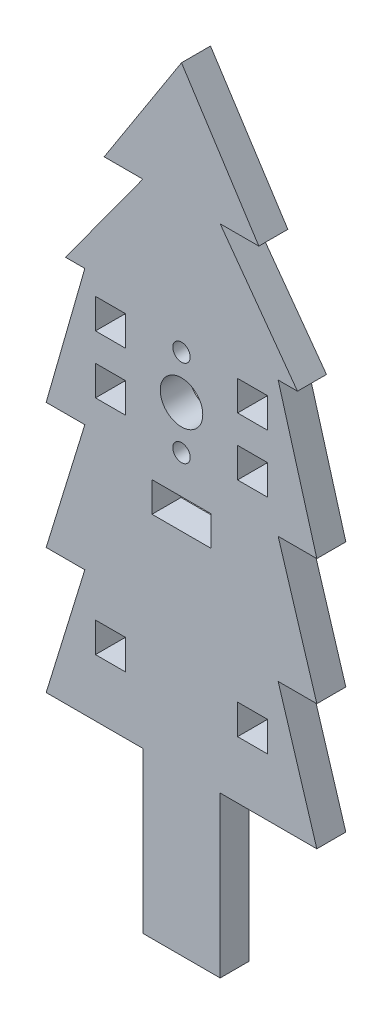
SolidWorks part; units mm, degrees
ref_plane "Ebene vorne (XY)" through (0, 0, 0) normal (0, 0, 1) x (1, 0, 0)
ref_plane "Ebene oben  (XZ)" through (0, 0, 0) normal (0, 1, 0) x (1, 0, 0)
ref_plane "Ebene rechts  (YZ)" through (0, 0, 0) normal (1, 0, 0) x (0, 0, -1)
ref_axis "x-Achse" through (-15.4, 0, 0) along (1, 0, 0)
ref_axis "y-Achse" through (0, 34.4272, 0) along (0, -1, 0)
ref_axis "z-Achse" through (0, 0, -0.15) along (0, 0, 1)
sketch "Profile_Laser_profile_3mm" plane through (0, 0, 0) normal (0, 0, 1) x (1, 0, 0)
  line L0 (0, 30.4272) -> (8, 18)
  line L1 (8, 18) -> (4, 18)
  line L2 (4, 18) -> (12, 7)
  line L3 (12, 7) -> (10, 7)
  line L4 (10, 7) -> (14, -7)
  line L5 (14, -7) -> (10, -7)
  line L6 (10, -7) -> (14, -20)
  line L7 (14, -20) -> (10, -20)
  line L8 (10, -20) -> (14, -33)
  line L9 (14, -33) -> (4, -33)
  line L10 (4, -33) -> (4, -49.5728)
  line L11 (4, -49.5728) -> (-4, -49.5728)
  line L12 (-4, -49.5728) -> (-4, -33)
  line L13 (-4, -33) -> (-14, -33)
  line L14 (-14, -33) -> (-10, -20)
  line L15 (-10, -20) -> (-14, -20)
  line L16 (-14, -20) -> (-10, -7)
  line L17 (-10, -7) -> (-14, -7)
  line L18 (-14, -7) -> (-10, 7)
  line L19 (-10, 7) -> (-12, 7)
  line L20 (-12, 7) -> (-4, 18)
  line L21 (-4, 18) -> (-8, 18)
  line L22 (-8, 18) -> (0, 30.4272)
  line L23 (-8.9, 1.95) -> (-5.8, 1.95)
  line L24 (-5.8, 1.95) -> (-5.8, 5.05)
  line L25 (-5.8, 5.05) -> (-8.9, 5.05)
  line L26 (-8.9, 5.05) -> (-8.9, 1.95)
  line L27 (-8.9, -4.05) -> (-5.8, -4.05)
  line L28 (-5.8, -4.05) -> (-5.8, -0.95)
  line L29 (-5.8, -0.95) -> (-8.9, -0.95)
  line L30 (-8.9, -0.95) -> (-8.9, -4.05)
  line L31 (-8.9, -27.05) -> (-5.8, -27.05)
  line L32 (-5.8, -27.05) -> (-5.8, -23.95)
  line L33 (-5.8, -23.95) -> (-8.9, -23.95)
  line L34 (-8.9, -23.95) -> (-8.9, -27.05)
  line L35 (5.8, 1.95) -> (8.9, 1.95)
  line L36 (8.9, 1.95) -> (8.9, 5.05)
  line L37 (8.9, 5.05) -> (5.8, 5.05)
  line L38 (5.8, 5.05) -> (5.8, 1.95)
  line L39 (5.8, -4.05) -> (8.9, -4.05)
  line L40 (8.9, -4.05) -> (8.9, -0.95)
  line L41 (8.9, -0.95) -> (5.8, -0.95)
  line L42 (5.8, -0.95) -> (5.8, -4.05)
  line L43 (5.8, -27.05) -> (8.9, -27.05)
  line L44 (8.9, -27.05) -> (8.9, -23.95)
  line L45 (8.9, -23.95) -> (5.8, -23.95)
  line L46 (5.8, -23.95) -> (5.8, -27.05)
  line L47 (-3.05, -11.55) -> (3.05, -11.55)
  line L48 (3.05, -11.55) -> (3.05, -8.45)
  line L49 (3.05, -8.45) -> (-3.05, -8.45)
  line L50 (-3.05, -8.45) -> (-3.05, -11.55)
  circle A0 centre (0, 0) radius 2.2
  circle A1 centre (0, -4.5) radius 0.9
  circle A2 centre (0, 4.5) radius 0.9
extrude "Laser_profile_3mm" add sketch "Profile_Laser_profile_3mm" along normal blind 3
